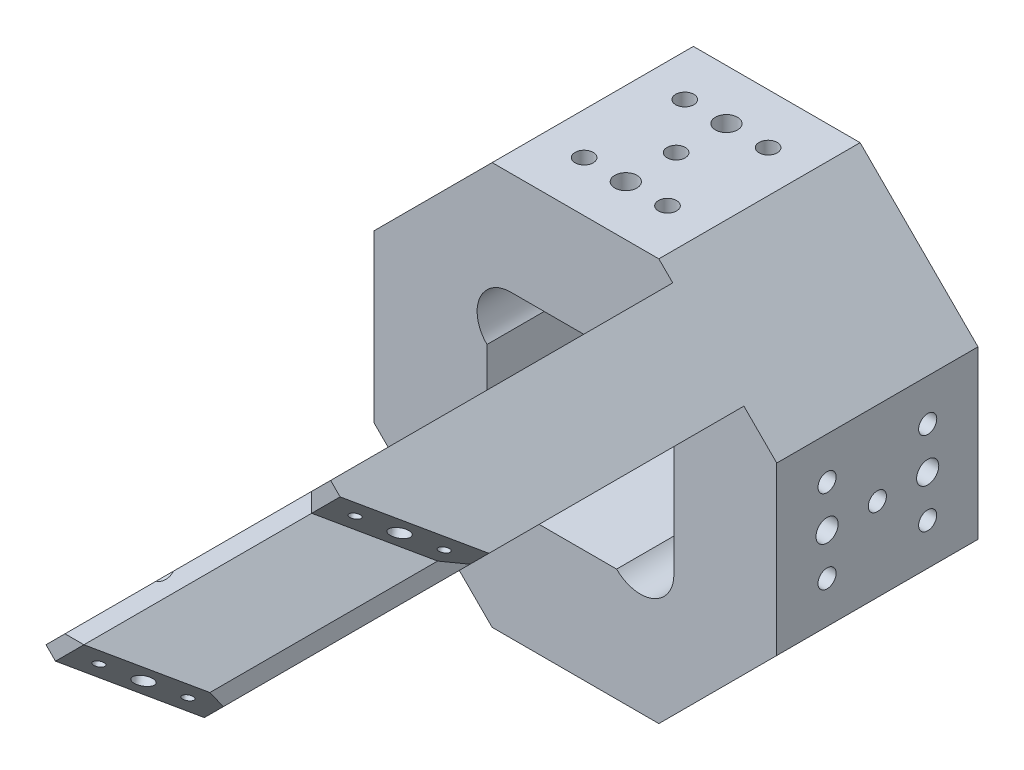
SolidWorks part; units mm, degrees
ref_plane "Front Plane" through (0, 0, 0) normal (0, 0, 1) x (1, 0, 0)
ref_plane "Top Plane" through (0, 0, 0) normal (0, 1, 0) x (1, 0, 0)
ref_plane "Right Plane" through (0, 0, 0) normal (1, 0, 0) x (0, 0, -1)
sketch "Sketch1" plane through (0, 0, 0) normal (0, 0, 1) x (1, 0, 0)
  line L0 (-12.4264, -30) -> (12.4264, -30)
  line L1 (30, -12.4264) -> (30, 12.4264)
  line L2 (30, 12.4264) -> (12.4264, 30)
  line L3 (12.4264, 30) -> (-12.4264, 30)
  line L4 (-12.4264, 30) -> (-30, 12.4264)
  line L5 (-30, 12.4264) -> (-30, -12.4264)
  line L6 (-30, -12.4264) -> (-12.4264, -30)
  line L7 (12.4264, -30) -> (30, -12.4264)
  line L9 (-13.2, 13.2) -> (13.2, 13.2)
  line L10 (-13.2, 13.2) -> (-13.2, -13.2)
  line L11 (-13.2, -13.2) -> (13.2, -13.2)
  line L12 (13.2, 13.2) -> (13.2, -13.2)
  line L13 (-13.2, 13.2) -> (13.2, -13.2) construction
  line L14 (-13.2, -13.2) -> (13.2, 13.2) construction
  circle A0 centre (0, 0) radius 30 construction
  dimension "D1" = 60
  dimension "D2" = 26.4
extrude "Boss-Extrude1" add sketch "Sketch1" along normal blind 30
sketch "Sketch2" plane through (0, 0, 30) normal (0, 0, 1) x (1, 0, 0)
  line L0 (-12.4264, 30) -> (-30, 12.4264) construction
  line L1 (-30, 12.4264) -> (-25.0503, 7.4767) construction
  line L2 (-25.0503, 7.4767) -> (-7.4767, 25.0503) construction
  line L3 (-7.4767, 25.0503) -> (-12.4264, 30) construction
  line L4 (12.4264, -30) -> (30, -12.4264) construction
  line L5 (30, -12.4264) -> (25.0503, -7.4767) construction
  line L6 (25.0503, -7.4767) -> (7.4767, -25.0503) construction
  line L7 (7.4767, -25.0503) -> (12.4264, -30) construction
  line L8 (14.4957, 27.9307) -> (25.1023, 17.3241)
  line L9 (25.1023, 17.3241) -> (20.8597, 13.0815)
  line L10 (20.8597, 13.0815) -> (10.253, 23.6881)
  line L11 (10.253, 23.6881) -> (14.4957, 27.9307)
  line L12 (-27.9307, -14.4957) -> (-17.3241, -25.1023)
  line L13 (-17.3241, -25.1023) -> (-13.0815, -20.8597)
  line L14 (-13.0815, -20.8597) -> (-23.6881, -10.253)
  line L15 (-23.6881, -10.253) -> (-27.9307, -14.4957)
  line L16 (30, 12.4264) -> (12.4264, 30) construction
  line L17 (21.2132, 21.2132) -> (13.2, 13.2) construction
  line L18 (-30, -12.4264) -> (-12.4264, -30) construction
  dimension "D1" = 7
  dimension "D2" = 6
  dimension "D3" = 5.5
  dimension "D4" = 9.5
extrude "Boss-Extrude2" add sketch "Sketch2" along normal blind 53
sketch "Sketch3" plane through (21.2132, 21.2132, 0) normal (0.7071, 0.7071, 0) x (0, 0, -1)
  line L3 (-83, 9.5) -> (-83, -5.5)
  line L4 (-83, 9.5) -> (-68, -5.5)
  line L5 (-83, -5.5) -> (-30, -5.5) construction
  line L6 (-68, -5.5) -> (-83, -5.5)
  dimension "D1" = 45
extrude "Cut-Extrude1" cut sketch "Sketch3" against normal through all
ref_plane "Plane1" through (26.7362, -26.7362, 37.8107) normal (0.5, -0.5, 0.7071) x (0.866, 0.2887, -0.4082)
ref_axis "Axis1" through (0, 0, 0) along (0, 0, -1)
ref_point "Point1"
hole_wizard "#6-32 Tapped Hole1" positions "Sketch14" profile "Sketch15" tap size "#6-32" standard "ANSI Inch" end condition through all
sketch "Sketch14" plane through (26.7362, -26.7362, 37.8107) normal (0.5, -0.5, 0.7071) x (0.866, 0.2887, -0.4082)
  line L7 (-52.9177, 28.0715) -> (-8.8269, 59.2484) construction
  line L9 (-57.3589, 39.5485) -> (-62.2579, 36.0844) construction
  line L10 (-8.8269, 59.2484) -> (-3.4701, 51.6728) construction
  line L11 (-5.9196, 49.9408) -> (-1.0206, 53.4049) construction
  point P0 (-8.8269, 59.2484)
  point P19 (-52.9177, 28.0715)
sketch "Sketch15" plane through (19.0919, 19.0919, 75.6213) normal (0.7071, 0.7071, 0) x (0.5, -0.5, -0.7071)
  line L0 (0, 0) -> (0, 83.4723)
  line L1 (0, 83.4723) -> (1.3525, 83.4723)
  line L2 (1.3525, 83.4723) -> (1.3525, 0)
  line L5 (1.3525, 0) -> (0, 0)
  line L11 (0, -6.35) -> (0, 107.95) construction
  dimension "Thru Tap Drill Dia." = 2.7051
  dimension "Thru Tap Drill Depth" = 83.4723
cosmetic thread "Hole Thread7" parameters "D2"=3.5052
cosmetic thread "Hole Thread8" parameters "D2"=3.5052
hole_wizard "#1-72 Tapped Hole1" positions "Sketch18" profile "Sketch19" tap size "#1-72" standard "ANSI Inch" end condition through all
sketch "Sketch18" plane through (25.9862, -25.9862, 36.75) normal (0.5, -0.5, 0.7071) x (0.866, 0.2887, -0.4082)
  line L0 (-8.8269, 59.2484) -> (-12.0023, 63.7392) construction
  line L2 (-8.8269, 59.2484) -> (-5.6514, 54.7577) construction
  line L13 (-18.167, 67.2613) -> (-5.9196, 49.9408) construction
  line L14 (-5.9196, 49.9408) -> (-18.167, 67.2613) construction
  line L16 (-5.9196, 49.9408) -> (-1.0206, 53.4049) construction
  line L17 (-52.9177, 28.0715) -> (-56.0931, 32.5623) construction
  line L19 (-52.9177, 28.0715) -> (-49.7423, 23.5808) construction
  line L21 (-50.0104, 18.7639) -> (-62.2579, 36.0844) construction
  point P0 (-12.0023, 63.7392)
  point P2 (-5.6514, 54.7577)
  point P4 (-56.0931, 32.5623)
  point P6 (-49.7423, 23.5808)
  dimension "D1" = 11
  dimension "D2" = 11
sketch "Sketch19" plane through (15.5919, 22.5919, 78.4497) normal (0.7071, 0.7071, 0) x (0.5, -0.5, -0.7071)
  line L0 (0, 0) -> (0, 81.9723)
  line L1 (0, 81.9723) -> (0.7556, 81.9723)
  line L2 (0.7556, 81.9723) -> (0.7556, 0)
  line L5 (0.7556, 0) -> (0, 0)
  line L11 (0, -6.35) -> (0, 107.95) construction
  dimension "Thru Tap Drill Dia." = 1.5113
  dimension "Thru Tap Drill Depth" = 81.9723
cosmetic thread "Hole Thread9" parameters "D2"=1.8542
cosmetic thread "Hole Thread10" parameters "D2"=1.8542
cosmetic thread "Hole Thread11" parameters "D2"=1.8542
cosmetic thread "Hole Thread12" parameters "D2"=1.8542
chamfer "Chamfer1" distance 2 angle 45 4 edges at (10.253, 23.6881, 56.5) (20.8597, 13.0815, 49) (-23.6881, -10.253, 56.5) (-13.0815, -20.8597, 49)
hole_wizard "M4x0.7 Tapped Hole1" positions "Sketch4" profile "Sketch6" tap size "M4x0.7" standard "ANSI Metric"
sketch "Sketch4" plane through (-30, 0, 0) normal (-1, 0, 0) x (0, 0, 1)
  line L3 (0, 0) -> (7.5, 0) construction
  line L4 (0, 12.4264) -> (0, -12.4264) construction
  line L5 (7.5, 0) -> (15, 0) construction
  line L6 (15, 0) -> (22.5, 0) construction
  line L7 (22.5, 0) -> (30, 0) construction
  line L8 (30, 12.4264) -> (30, -12.4264) construction
  point P0 (7.5, 0)
  point P2 (22.5, 0)
sketch "Sketch6" plane through (-30, 0, 7.5) normal (0, 1, 0) x (0, 0, 1)
  line L0 (0, 0) -> (0, 11.0914)
  line L1 (0, 11.0914) -> (1.65, 10.1)
  line L2 (1.65, 10.1) -> (1.65, 0)
  line L5 (1.65, 0) -> (0, 0)
  line L10 (0, 11.0914) -> (-1.65, 10.1) construction
  line L11 (0, -6.35) -> (0, 107.95) construction
  dimension "Tap Drill Dia." = 3.3
  dimension "Tap Drill Depth" = 10.1
  dimension "Drill Angle" = 118
cosmetic thread "Hole Thread1" parameters "D1"=8, "D2"=4
cosmetic thread "Hole Thread2" parameters "D1"=8, "D2"=4
hole_wizard "M4x0.7 Tapped Hole2" positions "Sketch7" profile "Sketch8" tap size "M4x0.7" standard "ANSI Metric"
sketch "Sketch7" plane through (0, -30, 0) normal (0, -1, 0) x (-1, 0, 0)
  line L0 (0, 0) -> (0, -7.5) construction
  line L1 (12.4264, 0) -> (-12.4264, 0) construction
  line L2 (0, -7.5) -> (0, -15) construction
  line L3 (0, -15) -> (0, -22.5) construction
  line L4 (0, -22.5) -> (0, -30) construction
  line L5 (12.4264, -30) -> (-12.4264, -30) construction
  point P2 (0, -7.5)
  point P9 (0, -22.5)
sketch "Sketch8" plane through (0, -30, 22.5) normal (1, 0, 0) x (0, 0, -1)
  line L0 (0, 0) -> (0, 11.0914)
  line L1 (0, 11.0914) -> (1.65, 10.1)
  line L2 (1.65, 10.1) -> (1.65, 0)
  line L5 (1.65, 0) -> (0, 0)
  line L10 (0, 11.0914) -> (-1.65, 10.1) construction
  line L11 (0, -6.35) -> (0, 107.95) construction
  dimension "Tap Drill Dia." = 3.3
  dimension "Tap Drill Depth" = 10.1
  dimension "Drill Angle" = 118
cosmetic thread "Hole Thread3" parameters "D1"=8, "D2"=4
cosmetic thread "Hole Thread4" parameters "D1"=8, "D2"=4
hole_wizard "M4x0.7 Tapped Hole3" positions "Sketch9" profile "Sketch10" tap size "M4x0.7" standard "ANSI Metric"
sketch "Sketch9" plane through (21.2132, -21.2132, 0) normal (0.7071, -0.7071, 0) x (0, 0, -1)
  line L0 (0, 0) -> (-7.5, 0) construction
  line L1 (-7.5, 0) -> (-15, 0) construction
  line L2 (-15, 0) -> (-22.5, 0) construction
  line L3 (-22.5, 0) -> (-30, 0) construction
  point P1 (-7.5, 0)
  point P6 (-22.5, 0)
sketch "Sketch10" plane through (21.2132, -21.2132, 22.5) normal (0, 0, 1) x (0.7071, 0.7071, 0)
  line L0 (0, 0) -> (0, 11.0914)
  line L1 (0, 11.0914) -> (1.65, 10.1)
  line L2 (1.65, 10.1) -> (1.65, 0)
  line L5 (1.65, 0) -> (0, 0)
  line L10 (0, 11.0914) -> (-1.65, 10.1) construction
  line L11 (0, -6.35) -> (0, 107.95) construction
  dimension "Tap Drill Dia." = 3.3
  dimension "Tap Drill Depth" = 10.1
  dimension "Drill Angle" = 118
cosmetic thread "Hole Thread5" parameters "D1"=8, "D2"=4
cosmetic thread "Hole Thread6" parameters "D1"=8, "D2"=4
sketch "Sketch20" plane through (21.2132, 21.2132, 0) normal (0.7071, 0.7071, 0) x (0, 0, -1)
  line L0 (-83, 9.5) -> (-81, 9.5)
  line L1 (-83, 9.5) -> (-30, 9.5) construction
  line L2 (-81, 9.5) -> (-81, 7.5)
  line L3 (-68, -5.5) -> (-83, 9.5) construction
  line L4 (-81, 7.5) -> (-83, 9.5)
  dimension "D1" = 2
extrude "Cut-Extrude2" cut sketch "Sketch20" against normal through all
hole_wizard "M4x0.7 Tapped Hole4" positions "Sketch21" profile "Sketch23" tap size "M4x0.7" standard "ANSI Metric"
sketch "Sketch21" plane through (0, 30, 0) normal (0, 1, 0) x (1, 0, 0)
  line L0 (0, 0) -> (0, -7.5) construction
  line L1 (0, -7.5) -> (0, -15) construction
  line L2 (0, 0) -> (0, 28.0014) construction
  line L3 (0, -15) -> (0, -22.5) construction
  line L4 (0, -22.5) -> (0, -30) construction
  line L5 (12.4264, -30) -> (-12.4264, -30) construction
  point P0 (0, -7.5)
  point P2 (0, -22.5)
sketch "Sketch23" plane through (0, 30, 7.5) normal (1, 0, 0) x (0, 0, 1)
  line L0 (0, 0) -> (0, 11.0914)
  line L1 (0, 11.0914) -> (1.65, 10.1)
  line L2 (1.65, 10.1) -> (1.65, 0)
  line L5 (1.65, 0) -> (0, 0)
  line L10 (0, 11.0914) -> (-1.65, 10.1) construction
  line L11 (0, -6.35) -> (0, 107.95) construction
  dimension "Tap Drill Dia." = 3.3
  dimension "Tap Drill Depth" = 10.1
  dimension "Drill Angle" = 118
cosmetic thread "Hole Thread13" parameters "D1"=8, "D2"=4
cosmetic thread "Hole Thread14" parameters "D1"=8, "D2"=4
sketch "Sketch24" plane through (0, 0, 0) normal (0, 0, -1) x (-1, 0, 0)
  line L0 (-13.2, 13.2) -> (13.2, -13.2) construction
  line L1 (13.2, 13.2) -> (-13.2, -13.2) construction
  circle A0 centre (-9.6645, 9.6645) radius 5
  circle A1 centre (9.6645, 9.6645) radius 5
  circle A2 centre (9.6645, -9.6645) radius 5
  circle A3 centre (-9.6645, -9.6645) radius 5
  dimension "D1" = 10
extrude "Cut-Extrude3" cut sketch "Sketch24" against normal through all
sketch "Sketch25" plane through (0, 0, 0) normal (0, 0, -1) x (-1, 0, 0)
  line L0 (-13.2, -6.1289) -> (-13.2, 6.1289) construction
  line L1 (9.6645, 14.6645) -> (-9.6645, 14.6645)
  line L2 (9.6645, 14.6645) -> (9.6645, 13.2)
  line L3 (9.6645, 13.2) -> (-9.6645, 13.2)
  line L4 (-9.6645, 14.6645) -> (-9.6645, 13.2)
  line L5 (-14.6645, -9.6645) -> (-13.2, -9.6645)
  line L6 (-14.6645, -9.6645) -> (-14.6645, 9.6645)
  line L7 (-14.6645, 9.6645) -> (-13.2, 9.6645)
  line L8 (-13.2, -9.6645) -> (-13.2, 9.6645)
  line L9 (-6.1289, 13.2) -> (6.1289, 13.2) construction
  arc A0 (13.2, 6.1289) -> (6.1289, 13.2) centre (9.6645, 9.6645) ccw construction
  arc A1 (-13.2, -6.1289) -> (-6.1289, -13.2) centre (-9.6645, -9.6645) ccw construction
  arc A2 (-6.1289, 13.2) -> (-13.2, 6.1289) centre (-9.6645, 9.6645) ccw construction
  point P19 (-9.6645, 9.6645)
  point P22 (9.6645, 9.6645)
  point P25 (-9.6645, -9.6645)
extrude "Cut-Extrude4" cut sketch "Sketch25" against normal through all
hole_wizard "#6-32 Tapped Hole2" positions "Sketch26" profile "Sketch27" tap size "#6-32" standard "ANSI Inch" end condition up to next
sketch "Sketch26" plane through (0, 30, 0) normal (0, 1, 0) x (1, 0, 0)
  line L2 (12.4264, 0) -> (6.2132, -7.5) construction
  line L3 (6.2132, -7.5) -> (0, -15) construction
  line L4 (0, -15) -> (-6.2132, -22.5) construction
  line L5 (-6.2132, -22.5) -> (-12.4264, -30) construction
  line L7 (-12.4264, 0) -> (-6.2132, -7.5) construction
  line L8 (-6.2132, -7.5) -> (0, -15) construction
  line L9 (0, -15) -> (6.2132, -22.5) construction
  line L10 (6.2132, -22.5) -> (12.4264, -30) construction
  point P0 (0, -15)
  point P2 (-6.2132, -7.5)
  point P4 (6.2132, -7.5)
  point P6 (-6.2132, -22.5)
  point P8 (6.2132, -22.5)
  point P42 (6.2132, -22.5)
cosmetic thread "Hole Thread15" parameters "D2"=3.5052
cosmetic thread "Hole Thread16" parameters "D2"=3.5052
cosmetic thread "Hole Thread17" parameters "D2"=3.5052
cosmetic thread "Hole Thread18" parameters "D2"=3.5052
cosmetic thread "Hole Thread19" parameters "D2"=3.5052
sketch "Sketch27" plane through (0, 30, 15) normal (1, 0, 0) x (0, 0, 1)
  line L0 (0, 0) -> (0, 15.3355)
  line L1 (0, 15.3355) -> (1.3525, 15.3355)
  line L2 (1.3525, 15.3355) -> (1.3525, 0)
  line L5 (1.3525, 0) -> (0, 0)
  line L11 (0, -6.35) -> (0, 107.95) construction
  dimension "Thru Tap Drill Dia." = 2.7051
  dimension "Thru Tap Drill Depth" = 15.3355
hole_wizard "#6-32 Tapped Hole3" positions "Sketch28" profile "Sketch29" tap size "#6-32" standard "ANSI Inch" end condition up to next
sketch "Sketch28" plane through (30, 0, 0) normal (1, 0, 0) x (0, 0, -1)
  line L0 (0, 12.4264) -> (-7.5, 6.2132) construction
  line L1 (-7.5, 6.2132) -> (-15, 0) construction
  line L2 (-15, 0) -> (-22.5, -6.2132) construction
  line L3 (-22.5, -6.2132) -> (-30, -12.4264) construction
  line L5 (-30, 12.4264) -> (-22.5, 6.2132) construction
  line L6 (-22.5, 6.2132) -> (-15, 0) construction
  line L7 (-15, 0) -> (-7.5, -6.2132) construction
  line L8 (-7.5, -6.2132) -> (0, -12.4264) construction
  point P0 (-15, 0)
  point P2 (-7.5, 6.2132)
  point P4 (-22.5, -6.2132)
  point P6 (-22.5, 6.2132)
  point P8 (-7.5, -6.2132)
sketch "Sketch29" plane through (30, 0, 15) normal (0, 1, 0) x (0, 0, -1)
  line L0 (0, 0) -> (0, 15.3355)
  line L1 (0, 15.3355) -> (1.3525, 15.3355)
  line L2 (1.3525, 15.3355) -> (1.3525, 0)
  line L5 (1.3525, 0) -> (0, 0)
  line L11 (0, -6.35) -> (0, 107.95) construction
  dimension "Thru Tap Drill Dia." = 2.7051
  dimension "Thru Tap Drill Depth" = 15.3355
cosmetic thread "Hole Thread20" parameters "D2"=3.5052
cosmetic thread "Hole Thread21" parameters "D2"=3.5052
cosmetic thread "Hole Thread22" parameters "D2"=3.5052
cosmetic thread "Hole Thread23" parameters "D2"=3.5052
cosmetic thread "Hole Thread24" parameters "D2"=3.5052
hole_wizard "M4x0.7 Tapped Hole6" positions "Sketch30" profile "Sketch32" tap size "M4x0.7" standard "ANSI Metric"
sketch "Sketch30" plane through (30, 0, 0) normal (1, 0, 0) x (0, 0, -1)
  line L0 (0, 0) -> (-7.5, 0) construction
  line L1 (-7.5, 0) -> (-15, 0) construction
  line L2 (0, 0) -> (28.0014, 0) construction
  line L3 (-15, 0) -> (-22.5, 0) construction
  line L4 (-22.5, 0) -> (-30, 0) construction
  line L5 (-30, -12.4264) -> (-30, 12.4264) construction
  point P0 (-22.5, 0)
  point P2 (-7.5, 0)
  point P19 (-7.5, 0)
  point P20 (-22.5, 0)
sketch "Sketch32" plane through (30, 0, 22.5) normal (0, 1, 0) x (0, 0, -1)
  line L0 (0, 0) -> (0, 11.0914)
  line L1 (0, 11.0914) -> (1.65, 10.1)
  line L2 (1.65, 10.1) -> (1.65, 0)
  line L5 (1.65, 0) -> (0, 0)
  line L10 (0, 11.0914) -> (-1.65, 10.1) construction
  line L11 (0, -6.35) -> (0, 107.95) construction
  dimension "Tap Drill Dia." = 3.3
  dimension "Tap Drill Depth" = 10.1
  dimension "Drill Angle" = 118
cosmetic thread "Hole Thread25" parameters "D1"=8, "D2"=4
cosmetic thread "Hole Thread26" parameters "D1"=8, "D2"=4
